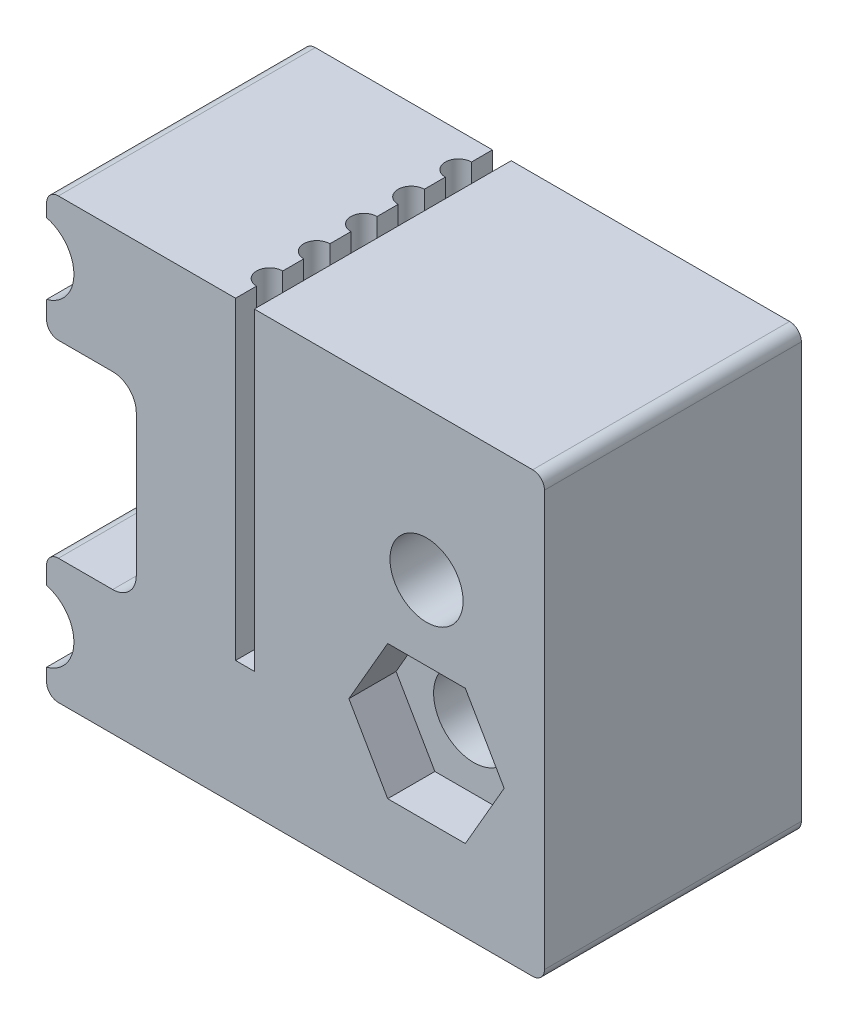
SolidWorks part; units mm, degrees
material "PET"
ref_plane "Front Plane" through (0, 0, 0) normal (0, 0, 1) x (1, 0, 0)
ref_plane "Top Plane" through (0, 0, 0) normal (0, 1, 0) x (1, 0, 0)
ref_plane "Right Plane" through (0, 0, 0) normal (1, 0, 0) x (0, 0, -1)
sketch "Sketch1" plane through (0, 0, 0) normal (0, 0, 1) x (1, 0, 0)
  line L5 (0, 13.8) -> (0, 14.5507)
  line L7 (0.5, 0) -> (20.6038, 0)
  line L9 (0, 17.5493) -> (0, 18.1)
  line L16 (20.6038, 18.6) -> (0.5, 18.6)
  line L17 (2.8, 13.3) -> (0.5, 13.3)
  line L19 (0.5, 5.3) -> (2.8, 5.3)
  line L21 (3.8, 12.3) -> (3.8, 6.3)
  line L23 (0, 0.5) -> (0, 1.0507)
  line L24 (0, 4.8) -> (0, 4.0493)
  line L29 (21.1038, 18.1) -> (21.1038, 0.5)
  circle A7 centre (16.1038, 12.3) radius 1.55
  circle A8 centre (16.1038, 6.3) radius 1.7
  arc A10 (0, 14.5507) -> (0, 17.5493) centre (-0.3932, 16.05) ccw
  arc A12 (2.8, 13.3) -> (3.8, 12.3) centre (2.8, 12.3) cw
  arc A13 (3.8, 6.3) -> (2.8, 5.3) centre (2.8, 6.3) cw
  arc A14 (0, 1.0507) -> (0, 4.0493) centre (-0.3932, 2.55) ccw
  arc A21 (0.5, 0) -> (0, 0.5) centre (0.5, 0.5) cw
  arc A22 (0, 4.8) -> (0.5, 5.3) centre (0.5, 4.8) cw
  arc A23 (0, 18.1) -> (0.5, 18.6) centre (0.5, 18.1) cw
  arc A24 (0.5, 13.3) -> (0, 13.8) centre (0.5, 13.8) cw
  arc A25 (21.1038, 18.1) -> (20.6038, 18.6) centre (20.6038, 18.1) ccw
  arc A26 (21.1038, 0.5) -> (20.6038, 0) centre (20.6038, 0.5) cw
extrude "Boss-Extrude2" add sketch "Sketch1" along normal blind 10.89
sketch "Sketch3" plane through (0, 18.6, 0) normal (0, 1, 0) x (1, 0, 0)
  line L1 (8.8038, -10.89) -> (8.8038, 0)
  line L2 (8.0088, -10.89) -> (8.8038, -10.89)
  line L3 (8.0088, -10) -> (8.0088, -10.89)
  line L7 (8.0088, -8) -> (8.0088, -8.89)
  line L8 (8.0088, -6) -> (8.0088, -6.89)
  line L9 (8.0088, -4) -> (8.0088, -4.89)
  line L10 (8.0088, -2) -> (8.0088, -2.89)
  line L11 (8.0088, 0) -> (8.0088, -0.89)
  line L12 (8.0088, 0) -> (8.8038, 0)
  arc A0 (8.0088, -10) -> (8.0088, -8.89) centre (8.0088, -9.445) cw
  arc A4 (8.0088, -4) -> (8.0088, -2.89) centre (8.0088, -3.445) cw
  arc A5 (8.0088, -6) -> (8.0088, -4.89) centre (8.0088, -5.445) cw
  arc A6 (8.0088, -8) -> (8.0088, -6.89) centre (8.0088, -7.445) cw
  arc A7 (8.0088, -0.89) -> (8.0088, -2) centre (8.0088, -1.445) ccw
  point P7 (8.8038, -10.8422)
extrude "Cut-Extrude1" cut sketch "Sketch3" against normal up to surface (13.3 mm away) up to face at (1.65, 5.3, 5.445)
sketch "Sketch4" plane through (0, 0, 10.89) normal (0, 0, 1) x (1, 0, 0)
  line L1 (19.3947, 6.3) -> (17.7493, 9.15)
  line L2 (17.7493, 9.15) -> (14.4584, 9.15)
  line L3 (14.4584, 9.15) -> (12.813, 6.3)
  line L4 (12.813, 6.3) -> (14.4584, 3.45)
  line L5 (14.4584, 3.45) -> (17.7493, 3.45)
  line L6 (17.7493, 3.45) -> (19.3947, 6.3)
  circle A0 centre (16.1038, 6.3) radius 2.85 construction
extrude "Cut-Extrude2" cut sketch "Sketch4" against normal blind 2
